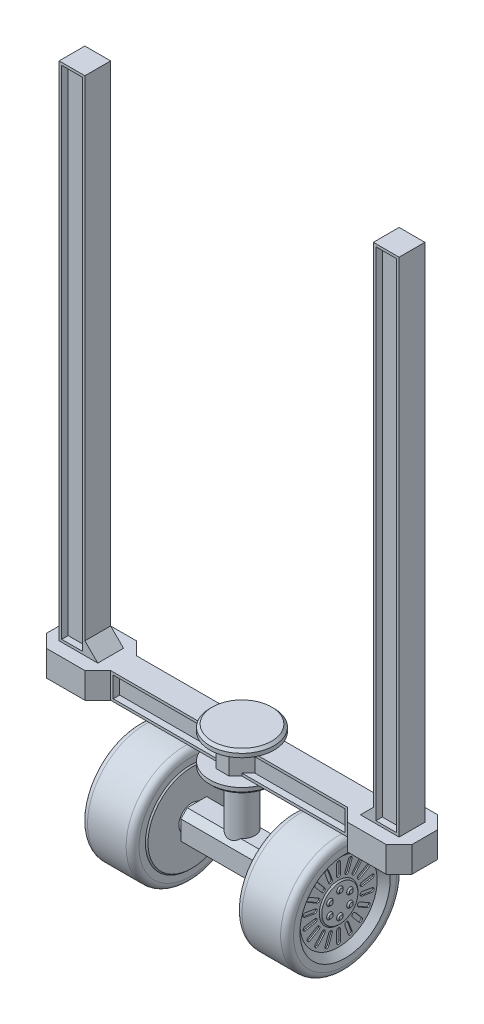
SolidWorks part; units mm, degrees
ref_plane "Front Plane" through (0, 0, 0) normal (0, 0, 1) x (1, 0, 0)
ref_plane "Top Plane" through (0, 0, 0) normal (0, 1, 0) x (1, 0, 0)
ref_plane "Right Plane" through (0, 0, 0) normal (1, 0, 0) x (0, 0, -1)
sketch "Sketch1" plane through (0, 0, 0) normal (0, 1, 0) x (1, 0, 0)
  line L0 (-100, 0) -> (2540, 0) construction
  line L1 (-100, -100) -> (100, -100)
  line L2 (-100, -100) -> (-100, 100)
  line L3 (-100, 100) -> (100, 100)
  line L4 (100, -100) -> (100, 100)
  line L5 (-100, -100) -> (100, 100) construction
  line L6 (-100, 100) -> (100, -100) construction
  line L8 (2340, -100) -> (2540, -100)
  line L9 (2340, -100) -> (2340, 100)
  line L10 (2340, 100) -> (2540, 100)
  line L11 (2540, -100) -> (2540, 100)
  line L12 (2340, -100) -> (2540, 100) construction
  line L13 (2340, 100) -> (2540, -100) construction
  point P0 (0, 0)
  point P8 (2440, 0)
  dimension "D1" = 200
  dimension "D2" = 200
  dimension "D3" = 2640
  dimension "D4" = 200
  dimension "D5" = 200
extrude "Boss-Extrude1" add sketch "Sketch1" along normal blind 4000
sketch "Sketch2" plane through (0, 0, 0) normal (0, -1, 0) x (1, 0, 0)
  line L8 (200, -200) -> (200, 200)
  line L9 (200, 200) -> (-200, 200)
  line L10 (-200, 200) -> (-200, -200)
  line L11 (-200, -200) -> (200, -200)
  line L12 (200, -200) -> (200, 200)
  line L13 (200, 200) -> (-200, 200)
  line L14 (-200, 200) -> (-200, -200)
  line L15 (-200, -200) -> (200, -200)
  line L16 (200, 0) -> (2240, 0) construction
  line L18 (200, -100) -> (2240, -100)
  line L19 (200, -100) -> (200, 100)
  line L20 (2640, -200) -> (2640, 200)
  line L21 (2640, 200) -> (2240, 200)
  line L22 (2240, 200) -> (2240, -200)
  line L23 (2240, -200) -> (2640, -200)
  line L24 (2640, -200) -> (2640, 200)
  line L25 (2640, 200) -> (2240, 200)
  line L26 (2240, 200) -> (2240, -200)
  line L27 (2240, -200) -> (2640, -200)
  line L28 (200, 100) -> (2240, 100)
  line L29 (2240, -100) -> (2240, 100)
  line L30 (200, -100) -> (2240, 100) construction
  line L31 (200, 100) -> (2240, -100) construction
  point P2 (1220, 0)
  line M9 (100, -100) -> (100, 100)
  line M10 (100, 100) -> (-100, 100)
  line M11 (-100, 100) -> (-100, -100)
  line M12 (-100, -100) -> (100, -100)
  dimension "D3" = 200
  dimension "D1" = 100
  dimension "D2" = 100
extrude "Boss-Extrude2" add sketch "Sketch2" along normal blind 100 and the other way blind 100 contours L14 L15 L12 L13 M9 M12 M11 M10 | L28 L12 L18 L26 | L26 L27 L24 L25 region at (0, 0, -194.3431) region at (1220, 0, 0) region at (2440, 0, 0)
chamfer "Chamfer1" distance 100 angle 45 8 edges at (-200, 0, -200) (-200, 0, 200) (2640, 0, 200) (2640, 0, -200) (2240, 0, -100) (200, 0, -100) (2240, 0, 100) (200, 0, 100)
combine bodies "Combine3" operation type add bodies to combine 103 101
chamfer "Chamfer2" distance 100 angle 45 2 edges at (2340, 100, 0) (100, 100, 0)
sketch "Sketch4" plane through (0, 0, 100) normal (0, 0, 1) x (1, 0, 0)
  line L8 (320, -80) -> (2120, -80)
  line L9 (2120, -80) -> (2120, 80)
  line L10 (2120, 80) -> (320, 80)
  line L11 (320, 80) -> (320, -80)
  line L12 (320, -80) -> (2120, -80)
  line L13 (2120, -80) -> (2120, 80)
  line L14 (2120, 80) -> (320, 80)
  line L15 (320, 80) -> (320, -80)
  dimension "D1" = 20
extrude "Cut-Extrude1" cut sketch "Sketch4" against normal blind 50
sketch "Sketch5" plane through (0, 0, -100) normal (0, 0, -1) x (-1, 0, 0)
  line L4 (-320, -80) -> (-320, 80)
  line L5 (-2120, -80) -> (-320, -80)
  line L6 (-2120, 80) -> (-2120, -80)
  line L7 (-320, 80) -> (-2120, 80)
  line L8 (-320, -80) -> (-320, 80)
  line L9 (-2120, -80) -> (-320, -80)
  line L10 (-2120, 80) -> (-2120, -80)
  line L11 (-320, 80) -> (-2120, 80)
  dimension "D1" = 0
extrude "Cut-Extrude2" cut sketch "Sketch5" against normal blind 50
sketch "Sketch6" plane through (0, 0, 100) normal (0, 0, 1) x (1, 0, 0)
  line L1 (-100, 4000) -> (100, 4000) construction
  line L3 (0, 4000) -> (0, 100) construction
  line L4 (200, 100) -> (-100, 100) construction
  line L5 (-100, 4000) -> (-100, 100) construction
  line L6 (-80, 120) -> (80, 120)
  line L7 (-80, 120) -> (-80, 3980)
  line L8 (-80, 3980) -> (80, 3980)
  line L9 (80, 120) -> (80, 3980)
  line L10 (-80, 120) -> (80, 3980) construction
  line L11 (-80, 3980) -> (80, 120) construction
  line L12 (2440, 4000) -> (2440, 100) construction
  line L13 (2340, 4000) -> (2540, 4000) construction
  line L14 (2540, 100) -> (2240, 100) construction
  line L15 (2540, 4000) -> (2540, 100) construction
  line L16 (2360, 120) -> (2520, 120)
  line L17 (2360, 120) -> (2360, 3980)
  line L18 (2360, 3980) -> (2520, 3980)
  line L19 (2520, 120) -> (2520, 3980)
  line L20 (2360, 120) -> (2520, 3980) construction
  line L21 (2360, 3980) -> (2520, 120) construction
  point P0 (0, 2050)
  point P20 (2440, 2050)
  dimension "D1" = 20
  dimension "D2" = 20
  dimension "D3" = 20
  dimension "D4" = 20
extrude "Cut-Extrude3" cut sketch "Sketch6" against normal blind 50
sketch "Sketch7" plane through (0, 0, -100) normal (0, 0, -1) x (-1, 0, 0)
  line L0 (-2520, 120) -> (-2520, 3980) construction
  line L1 (-2520, 3980) -> (-2360, 3980) construction
  line L2 (-2360, 3980) -> (-2360, 120) construction
  line L3 (-2360, 120) -> (-2520, 120) construction
  line L4 (-80, 120) -> (-80, 3980) construction
  line L5 (-80, 3980) -> (80, 3980) construction
  line L6 (80, 3980) -> (80, 120) construction
  line L7 (80, 120) -> (-80, 120) construction
  line L8 (-2520, 120) -> (-2520, 3980)
  line L9 (-2520, 3980) -> (-2360, 3980)
  line L10 (-2360, 3980) -> (-2360, 120)
  line L11 (-2360, 120) -> (-2520, 120)
  line L12 (-80, 120) -> (-80, 3980)
  line L13 (-80, 3980) -> (80, 3980)
  line L14 (80, 3980) -> (80, 120)
  line L15 (80, 120) -> (-80, 120)
extrude "Cut-Extrude4" cut sketch "Sketch7" against normal blind 50
sketch "Sketch8" plane through (0, -100, 0) normal (0, -1, 0) x (1, 0, 0)
  line L0 (1220, 100) -> (1220, -100) construction
  line L1 (300, 100) -> (2140, 100) construction
  line L2 (300, -100) -> (2140, -100) construction
  circle A0 centre (1220, 0) radius 250
  dimension "D1" = 500
extrude "Boss-Extrude3" add sketch "Sketch8" along normal blind 50
sketch "Sketch9" plane through (0, 100, 0) normal (0, 1, 0) x (1, 0, 0)
  circle A1 centre (1220, 0) radius 250
  circle A2 centre (1220, 0) radius 250
  dimension "D1" = 0
extrude "Boss-Extrude4" add sketch "Sketch9" along normal blind 50
sketch "Sketch10" plane through (0, -100, 0) normal (0, 1, 0) x (1, 0, 0)
  line L0 (1220, -100) -> (1220, 100) construction
  line L1 (990.8712, -100) -> (1449.1288, -100) construction
  line L2 (990.8712, 100) -> (1449.1288, 100) construction
  line L4 (1070, 150) -> (1370, 150)
  line L5 (1070, 150) -> (1070, -150)
  line L6 (1070, -150) -> (1370, -150)
  line L7 (1370, 150) -> (1370, -150)
  line L8 (1070, 150) -> (1370, -150) construction
  line L9 (1070, -150) -> (1370, 150) construction
  point P6 (1220, 0)
  dimension "D1" = 300
  dimension "D2" = 300
extrude "Boss-Extrude5" add sketch "Sketch10" along normal up to surface (200 mm away) up to face at (1220, 100, 175)
chamfer "Chamfer3" distance 100 angle 45 4 edges at (1070, 0, -150) (1370, 0, -150) (1370, 0, 150) (1070, 0, 150)
sketch "Sketch11" plane through (0, -150, 0) normal (0, -1, 0) x (1, 0, 0)
  line L0 (1220, 250) -> (1220, -250) construction
  circle A0 centre (1220, 0) radius 250 construction
  circle A1 centre (1220, 0) radius 100
  dimension "D1" = 200
extrude "Boss-Extrude6" add sketch "Sketch11" along normal blind 400
sketch "Sketch12" plane through (0, -550, 0) normal (0, -1, 0) x (1, 0, 0)
  line L0 (1220, 100) -> (1220, -100) construction
  line L2 (870, -125) -> (1570, -125)
  line L3 (870, -125) -> (870, 125)
  line L4 (870, 125) -> (1570, 125)
  line L5 (1570, -125) -> (1570, 125)
  line L6 (870, -125) -> (1570, 125) construction
  line L7 (870, 125) -> (1570, -125) construction
  circle A0 centre (1220, 0) radius 100 construction
  circle A1 centre (1220, 0) radius 100 construction
  point P7 (1220, 0)
  dimension "D1" = 700
  dimension "D2" = 250
extrude "Boss-Extrude7" add sketch "Sketch12" along normal blind 250
chamfer "Chamfer4" distance 50 angle 45 4 edges at (1220, -800, -125) (1220, -800, 125) (1220, -550, -125) (1220, -550, 125)
sketch "Sketch13" plane through (870, 0, 0) normal (-1, 0, 0) x (0, 0, 1)
  line L0 (0, -550) -> (0, -800) construction
  line L1 (75, -550) -> (-75, -550) construction
  line L2 (75, -800) -> (-75, -800) construction
  circle A0 centre (0, -675) radius 100
  dimension "D1" = 200
extrude "Boss-Extrude8" add sketch "Sketch13" along normal blind 50 and the other way blind 750
chamfer "Chamfer5" distance 20 angle 45 2 edges at (1220, -150, -250) (1220, 150, 250)
sketch "Sketch14" plane through (820, 0, 0) normal (-1, 0, 0) x (0, 0, 1)
  line L0 (0, -575) -> (0, -775) construction
  circle A0 centre (0, -675) radius 100 construction
  circle A1 centre (0, -675) radius 100 construction
  circle A2 centre (0, -675) radius 450
  dimension "D1" = 900
extrude "Boss-Extrude9" add sketch "Sketch14" along normal blind 400
fillet "Fillet1" radius 50 2 edges at (420, -675, 450) (820, -675, 450)
sketch "Sketch15" plane through (420, 0, 0) normal (-1, 0, 0) x (0, 0, 1)
  circle A0 centre (0, -675) radius 350
  dimension "D1" = 700
extrude "Cut-Extrude5" cut sketch "Sketch15" against normal blind 50
sketch "Sketch16" plane through (820, 0, 0) normal (1, 0, 0) x (0, 0, -1)
  circle A0 centre (0, -675) radius 350
  dimension "D1" = 700
extrude "Boss-Extrude10" add sketch "Sketch16" along normal blind 10
chamfer "Chamfer7" distance 50 angle 45 1 edges at (470, -675, 350)
sketch "Sketch17" plane through (470, 0, 0) normal (-1, 0, 0) x (0, 0, 1)
  circle A0 centre (0, -675) radius 150
  dimension "D1" = 300
extrude "Boss-Extrude11" add sketch "Sketch17" along normal blind 10
chamfer "Chamfer8" distance 10 angle 45 2 edges at (830, -675, -350) (460, -675, 150)
ref_plane "Plane1" through (1220, 0, 0) normal (-1, 0, 0) x (0, 0, 1)
sketch "Sketch18" plane through (470, 0, 0) normal (-1, 0, 0) x (0, 0, 1)
  line L0 (0, -375) -> (0, -410) construction
  line L1 (0, -410) -> (0, -490) construction
  line L2 (0, -490) -> (0, -525) construction
  line L3 (0, -410) -> (0, -490) construction
  line L4 (15, -410) -> (15, -490)
  line L5 (-15, -410) -> (-15, -490)
  circle A0 centre (0, -675) radius 300 construction
  circle A1 centre (0, -675) radius 150 construction
  arc A2 (15, -410) -> (-15, -410) centre (0, -410) ccw
  arc A3 (-15, -490) -> (15, -490) centre (0, -490) ccw
  point P11 (0, -450)
  dimension "D1" = 80
  dimension "D2" = 30
extrude "Cut-Extrude6" cut sketch "Sketch18" against normal blind 10
pattern_circular "CirPattern1" count 18 over 360 about axis through (460, -675, 0) along (-1, 0, 0) of "Cut-Extrude6"
sketch "Sketch19" plane through (460, 0, 0) normal (-1, 0, 0) x (0, 0, 1)
  line L0 (0, -535) -> (0, -585) construction
  circle A0 centre (0, -675) radius 140 construction
  circle A1 centre (0, -585) radius 25
  dimension "D2" = 50
  dimension "D1" = 50
extrude "Boss-Extrude12" add sketch "Sketch19" along normal blind 10
pattern_circular "CirPattern2" count 6 over 360 about axis through (460, -675, 0) along (-1, 0, 0) of "Boss-Extrude12"
chamfer "Chamfer9" distance 10 angle 45 6 edges at (450, -651.6506, 90.4423) (450, -741.6506, 65.4423) (450, -765, -25) (450, -698.3494, -90.4423) (450, -585, 25) (450, -608.3494, -65.4423)
mirror "Mirror1" about plane through (1220, 0, 0) normal (-1, 0, 0) of "Chamfer9", "CirPattern2", "Boss-Extrude12", "CirPattern1", "Cut-Extrude6", "Boss-Extrude9", "Fillet1", "Cut-Extrude5", "Boss-Extrude10", "Chamfer7", "Boss-Extrude11", "Chamfer8"
